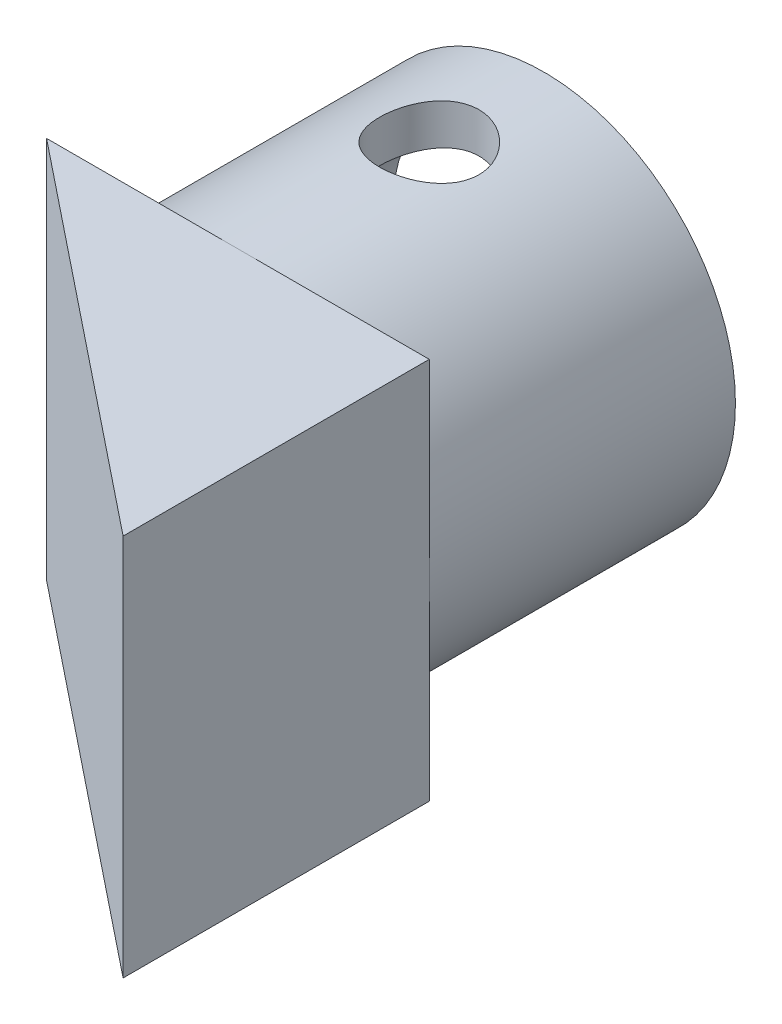
SolidWorks part; units mm, degrees
ref_plane "Front Plane" through (0, 0, 0) normal (0, 0, 1) x (1, 0, 0)
ref_plane "Top Plane" through (0, 0, 0) normal (0, 1, 0) x (1, 0, 0)
ref_plane "Right Plane" through (0, 0, 0) normal (1, 0, 0) x (0, 0, -1)
sketch "Sketch1" plane through (0, 0, 0) normal (0, 0, 1) x (1, 0, 0)
  circle A0 centre (0, 0) radius 3.95
  circle A1 centre (0, 0) radius 5
  dimension "D1" = 7.9
  dimension "D2" = 10
extrude "Boss-Extrude1" add sketch "Sketch1" along normal blind 8
sketch "Sketch3" plane through (0, 0, 0) normal (0, 1, 0) x (1, 0, 0)
  line L0 (5, -16) -> (-5, -8)
  line L1 (-5, -8) -> (5, -8)
  line L2 (5, -8) -> (5, -16)
  point P3 (5, -20.8696)
  dimension "D1" = 8
extrude "Boss-Extrude2" add sketch "Sketch3" along normal blind 5 and the other way blind 5
sketch "Sketch4" plane through (0, 0, 0) normal (0, 1, 0) x (1, 0, 0)
  line L2 (0, 0) -> (0, -8) construction
  line L3 (5, 0) -> (-5, 0) construction
  circle A0 centre (0, -3) radius 1.3
  point P2 (0, 0)
  point P3 (0, 0)
  dimension "D1" = 2.6
  dimension "D2" = 3
extrude "Cut-Extrude1" cut sketch "Sketch4" against normal through all and the other way through all
